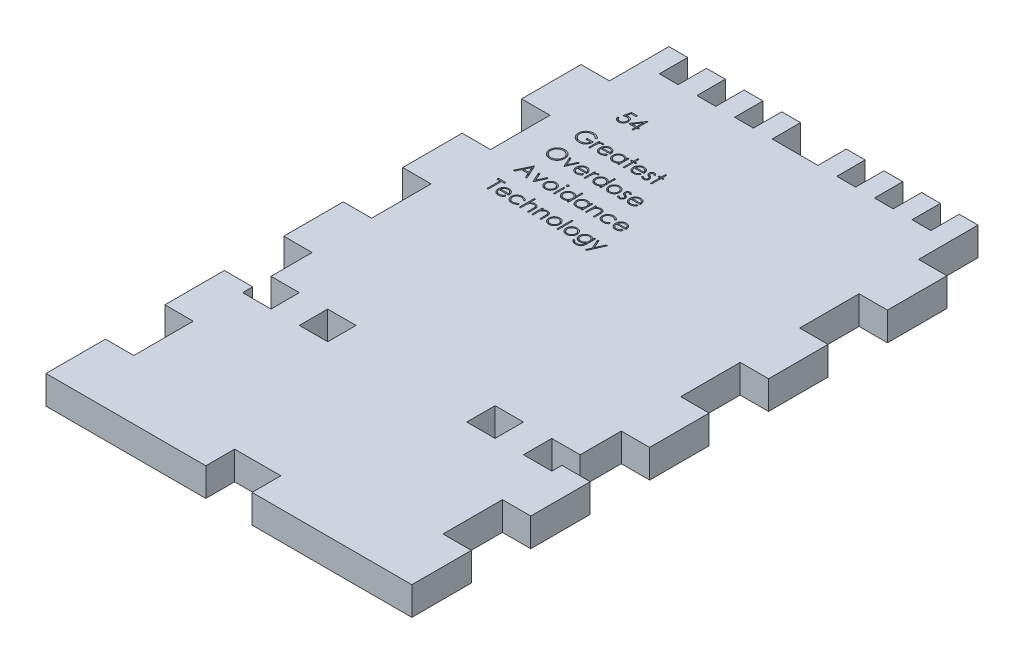
SolidWorks part; units mm, degrees
ref_plane "Front Plane" through (0, 0, 0) normal (0, 0, 1) x (1, 0, 0)
ref_plane "Top Plane" through (0, 0, 0) normal (0, 1, 0) x (1, 0, 0)
ref_plane "Right Plane" through (0, 0, 0) normal (1, 0, 0) x (0, 0, -1)
sketch "Sketch3" plane through (0, 0, 0) normal (0, 1, 0) x (1, 0, 0)
  line L1 (0, 0) -> (80, 0)
  line L2 (0, 0) -> (0, 130)
  line L3 (0, 130) -> (80, 130)
  line L4 (80, 0) -> (80, 130)
  line L9 (10.314, 130) -> (14.428, 130)
  line L10 (10.314, 130) -> (10.314, 123.8)
  line L11 (10.314, 123.8) -> (14.428, 123.8)
  line L12 (14.428, 130) -> (14.428, 123.8)
  line L13 (18.542, 130) -> (22.656, 130)
  line L14 (18.542, 130) -> (18.542, 123.8)
  line L15 (18.542, 123.8) -> (22.656, 123.8)
  line L16 (22.656, 130) -> (22.656, 123.8)
  line L17 (26.77, 130) -> (30.884, 130)
  line L18 (26.77, 130) -> (26.77, 123.8)
  line L19 (26.77, 123.8) -> (30.884, 123.8)
  line L20 (30.884, 130) -> (30.884, 123.8)
  line L25 (69.69, 130) -> (65.576, 130)
  line L26 (69.69, 130) -> (69.69, 123.8)
  line L27 (69.69, 123.8) -> (65.576, 123.8)
  line L28 (65.576, 130) -> (65.576, 123.8)
  line L29 (61.462, 130) -> (57.348, 130)
  line L30 (61.462, 130) -> (61.462, 123.8)
  line L31 (61.462, 123.8) -> (57.348, 123.8)
  line L32 (57.348, 130) -> (57.348, 123.8)
  line L33 (53.234, 130) -> (49.12, 130)
  line L34 (53.234, 130) -> (53.234, 123.8)
  line L35 (53.234, 123.8) -> (49.12, 123.8)
  line L36 (49.12, 130) -> (49.12, 123.8)
  line L37 (0, 130) -> (6.2, 130)
  line L38 (0, 130) -> (0, 117)
  line L39 (0, 117) -> (6.2, 117)
  line L40 (6.2, 130) -> (6.2, 117)
  line L41 (0, 104) -> (6.2, 104)
  line L42 (0, 104) -> (0, 91)
  line L43 (0, 91) -> (6.2, 91)
  line L44 (6.2, 104) -> (6.2, 91)
  line L45 (0, 78) -> (6.2, 78)
  line L46 (0, 78) -> (0, 65)
  line L47 (0, 65) -> (6.2, 65)
  line L48 (6.2, 78) -> (6.2, 65)
  line L49 (0, 52) -> (6.2, 52)
  line L50 (0, 52) -> (0, 39)
  line L51 (0, 39) -> (6.2, 39)
  line L52 (6.2, 52) -> (6.2, 39)
  line L53 (0, 26) -> (6.2, 26)
  line L54 (0, 26) -> (0, 13)
  line L55 (0, 13) -> (6.2, 13)
  line L56 (6.2, 26) -> (6.2, 13)
  line L57 (34.998, 130) -> (45.006, 130)
  line L58 (73.8, 130) -> (80, 130)
  line L59 (73.8, 130) -> (73.8, 117)
  line L60 (73.8, 117) -> (80, 117)
  line L61 (80, 130) -> (80, 117)
  line L62 (80, 104) -> (73.8, 104)
  line L63 (80, 104) -> (80, 91)
  line L64 (80, 91) -> (73.8, 91)
  line L65 (73.8, 104) -> (73.8, 91)
  line L66 (80, 78) -> (73.8, 78)
  line L67 (80, 78) -> (80, 65)
  line L68 (80, 65) -> (73.8, 65)
  line L69 (73.8, 78) -> (73.8, 65)
  line L70 (80, 52) -> (73.8, 52)
  line L71 (80, 52) -> (80, 39)
  line L72 (80, 39) -> (73.8, 39)
  line L73 (73.8, 52) -> (73.8, 39)
  line L74 (80, 26) -> (73.8, 26)
  line L75 (80, 26) -> (80, 13)
  line L76 (80, 13) -> (73.8, 13)
  line L77 (73.8, 26) -> (73.8, 13)
  line L78 (34.95, 0) -> (45.05, 0)
  line L79 (34.95, 0) -> (34.95, 6.3)
  line L80 (34.95, 6.3) -> (45.05, 6.3)
  line L81 (45.05, 0) -> (45.05, 6.3)
  line L82 (6.2, 43) -> (12.4, 43)
  line L83 (6.2, 43) -> (6.2, 36.8)
  line L84 (6.2, 36.8) -> (12.4, 36.8)
  line L85 (12.4, 43) -> (12.4, 36.8)
  line L86 (18.6, 43) -> (24.8, 43)
  line L87 (18.6, 43) -> (18.6, 36.8)
  line L88 (18.6, 36.8) -> (24.8, 36.8)
  line L89 (24.8, 43) -> (24.8, 36.8)
  line L90 (73.8, 43) -> (67.6, 43)
  line L91 (73.8, 43) -> (73.8, 36.8)
  line L92 (73.8, 36.8) -> (67.6, 36.8)
  line L93 (67.6, 43) -> (67.6, 36.8)
  line L94 (61.4, 43) -> (55.2, 43)
  line L95 (61.4, 43) -> (61.4, 36.8)
  line L96 (61.4, 36.8) -> (55.2, 36.8)
  line L97 (55.2, 43) -> (55.2, 36.8)
  line L98 (34.998, 130) -> (34.998, 123.8)
  line L99 (34.998, 123.8) -> (45.006, 123.8)
  line L100 (45.006, 130) -> (45.006, 123.8)
  point P67 (6.2, 43)
  dimension "D1" = 80
  dimension "D2" = 130
  dimension "D3" = 10.314
  dimension "D4" = 10.31
  dimension "D5" = 13
  dimension "D6" = 4.114
  dimension "D7" = 4.114
  dimension "D8" = 6.2
  dimension "D9" = 4.114
  dimension "D10" = 4.114
  dimension "D11" = 4.114
  dimension "D12" = 6.2
  dimension "D13" = 6.2
  dimension "D14" = 6.2
  dimension "D15" = 13
  dimension "D16" = 4.114
  dimension "D17" = 13
  dimension "D18" = 4.114
  dimension "D19" = 4.114
  dimension "D20" = 4.114
  dimension "D21" = 4.114
  dimension "D22" = 13
  dimension "D23" = 13
  dimension "D24" = 6.2
  dimension "D25" = 6.2
  dimension "D26" = 13
  dimension "D27" = 13
  dimension "D28" = 6.2
  dimension "D29" = 13
  dimension "D30" = 13
  dimension "D31" = 6.2
  dimension "D32" = 6.2
  dimension "D33" = 13
  dimension "D34" = 13
  dimension "D35" = 13
  dimension "D36" = 6.2
  dimension "D37" = 13
  dimension "D38" = 13
  dimension "D39" = 6.2
  dimension "D40" = 43
  dimension "D41" = 6.3
  dimension "D42" = 10.1
  dimension "D43" = 34.95
  dimension "D44" = 6.2
  dimension "D45" = 6.2
  dimension "D46" = 6.2
  dimension "D47" = 6.2
  dimension "D48" = 6.2
  dimension "D49" = 6.2
  dimension "D50" = 6.2
  dimension "D51" = 6.2
  dimension "D52" = 13
  dimension "D53" = 13
  dimension "D54" = 13
  dimension "D55" = 6.2
  dimension "D56" = 6.2
  dimension "D57" = 6.2
  dimension "D58" = 6.2
  dimension "D59" = 6.2
  dimension "D60" = 4.114
  dimension "D61" = 4.114
  dimension "D62" = 6.2
extrude "Boss-Extrude1" add sketch "Sketch3" along normal blind 6.2 contours L93 L90 L73 L70 L4 L68 L69 L66 L64 L65 L62 L60 L59 L3 L26 L27 L28 L30 L31 L32 L34 L35 L36 L20 L19 L18 L16 L15 L14 L12 L11 L10 L40 L39 L2 L41 L44 L43 L45 L48 L47 region at (40, 0, -63.8257)
sketch "Sketch6" plane through (0, 6.2, 0) normal (0, 1, 0) x (1, 0, 0)
  text T0 "54\r\n"
extrude "Cut-Extrude1" cut sketch "Sketch6" against normal blind 1 from surface starting at face at (58.3, 6.2, -39.9)
sketch "Sketch7" plane through (0, 6.2, 0) normal (0, 1, 0) x (1, 0, 0)
  text T0 "Greatest\r\nOverdose\r\nAvoidance\r\nTechnology"
extrude "Cut-Extrude2" cut sketch "Sketch7" against normal blind 1
